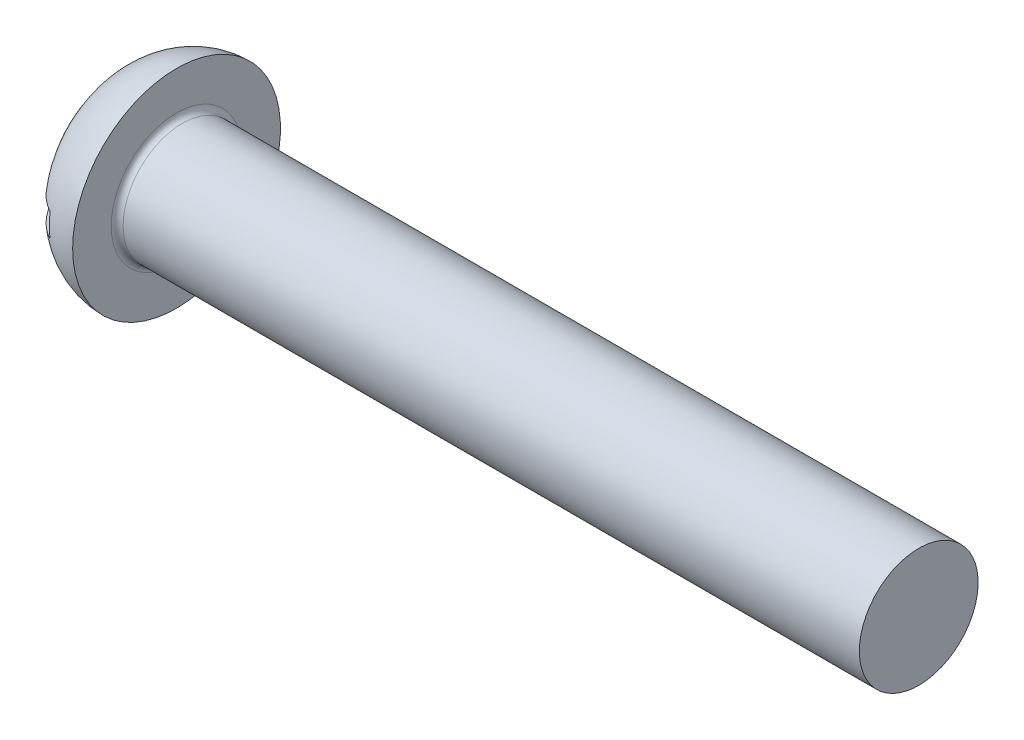
SolidWorks part; units mm, degrees
ref_plane "Front Plane" through (0, 0, 0) normal (0, 0, 1) x (1, 0, 0)
ref_plane "Top Plane" through (0, 0, 0) normal (0, 1, 0) x (1, 0, 0)
ref_plane "Right Plane" through (0, 0, 0) normal (1, 0, 0) x (0, 0, -1)
sketch "BodySke" plane through (0, 0, 0) normal (0, 0, 1) x (1, 0, 0)
  line L0 (0, 0) -> (111.3824, 0) construction
  line L1 (0, 0) -> (0, 8) construction
  line L2 (5.4, 4) -> (5.4, 7)
  line L4 (5.4, 4) -> (55.4, 4)
  line L5 (55.4, 4) -> (55.4, 0)
  line L6 (6.65, 7.824) -> (6.65, -6.8939) construction
  line L7 (0, 0) -> (55.4, 0)
  line L8 (25.4, 8.824) -> (25.4, -4.958) construction
  arc A0 (5.4, 7) -> (1.888, 5.306) centre (5.4541, 2.4003) ccw
  arc A1 (1.888, 5.306) -> (0, 0) centre (8.4, 0) ccw
  point P10 (55.4, 3.4455)
  dimension "Thread_minor" = 6.891
  dimension "Head_height" = 5.4
  dimension "Advance" = 1.25
  dimension "Length" = 50
  dimension "Head_dia" = 14
revolve "BaseBody" add sketch "BodySke" angle 360 about L0
cosmetic thread "ThreadCosmetic" [suppressed] parameters "Thread_minor"=6.891
fillet "Fillet1" radius 0.4 1 edges at (5.4, 0, 4)
sketch "SlotSke" plane through (0, 0, 0) normal (1, 0, 0) x (0, 0, -1)
  line L1 (7, 0.8) -> (-7, 0.8)
  line L3 (7, 0.8) -> (7, -0.8)
  line L5 (7, -0.8) -> (-7, -0.8)
  line L6 (-7, 0.8) -> (-7, -0.8)
  dimension "D1" = 14
  dimension "D2" = 7
  dimension "D4" = 0.8
extrude "Slot" cut sketch "SlotSke" along normal blind 3.3
sketch "ThdSchSke" plane through (0, 0, 0) normal (0, 0, 1) x (1, 0, 0)
  line L0 (0, 0) -> (55.1256, 0) construction
  line L1 (0, 0) -> (111.3824, 0) construction
  line L2 (55.0799, 4) -> (55.0799, 4.6403)
  line L3 (55.0799, 4.6403) -> (55.7201, 4.6403)
  line L4 (55.7201, 4.6403) -> (55.7201, 4)
  line L5 (55.7201, 4) -> (55.4, 3.4455)
  line L6 (55.4, 3.4455) -> (55.0799, 4)
  line L7 (5.4, 4) -> (55.4, 4) construction
  line L13 (55.4, 4) -> (55.4, 0) construction
revolve "ThreadSchematic" [suppressed] cut sketch "ThdSchSke" angle 360 about L0
pattern_linear "ThdSchPat" [suppressed] count 24 along (-1, 0, 0) of bodies 103
equation "\"Thread_minor@ThreadCosmetic\" = \"Thread_minor@BodySke\""
equation "\"Advance@ThdSchPat\" = \"Advance@BodySke\""
equation "\"D1@ThdSchPat\" =  int( \"Thread_length@BodySke\" / \"Advance@ThdSchPat\" ) "
equation "\"D1@SlotSke\" = \"Head_dia@BodySke\""
equation "\"D2@SlotSke\" = \"D1@SlotSke\" / 2"
equation "\"D4@SlotSke\" = \"Slot_width@SlotSke\" / 2"
